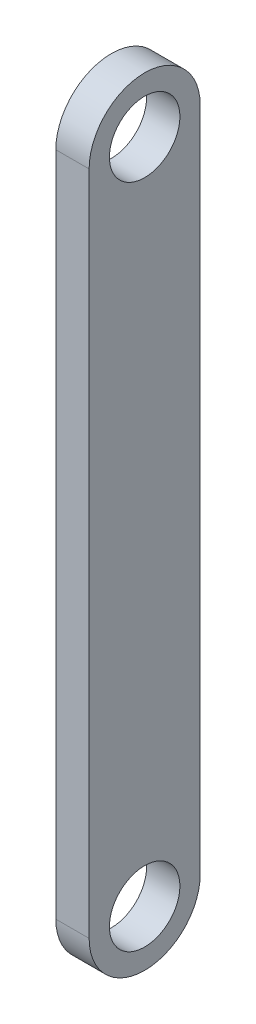
SolidWorks part; units mm, degrees
material "Acrylic (Medium-high impact)"
ref_plane "Alzado" through (0, 0, 0) normal (0, 0, 1) x (1, 0, 0)
ref_plane "Planta" through (0, 0, 0) normal (0, 1, 0) x (1, 0, 0)
ref_plane "Vista lateral" through (0, 0, 0) normal (1, 0, 0) x (0, 0, -1)
sketch "Sketch3" plane through (0, 0, 0) normal (1, 0, 0) x (0, 0, -1)
  line L1 (-5, -35) -> (5, -35)
  line L2 (-5, -35) -> (-5, 35)
  line L3 (-5, 35) -> (5, 35)
  line L4 (5, -35) -> (5, 35)
  line L5 (-5, -35) -> (5, 35) construction
  line L6 (-5, 35) -> (5, -35) construction
  point P0 (0, 0)
  dimension "D1" = 70
  dimension "D2" = 10
extrude "Boss-Extrude1" add sketch "Sketch3" along normal blind 3 contours L3 L4 L1 L2
sketch "Sketch4" plane through (3, 0, 0) normal (1, 0, 0) x (0, 0, -1)
  line L0 (0, 0) -> (0, -35) construction
  line L1 (-5, -35) -> (5, -35) construction
  line L2 (0, 0) -> (0, 35) construction
  line L3 (-5, 35) -> (5, 35) construction
  line L4 (0, 0) -> (0, 30) construction
  line L5 (0, 0) -> (0, -30) construction
  circle A0 centre (0, 30) radius 3.175
  circle A1 centre (0, -30) radius 3.175
  dimension "D1" = 30
  dimension "D2" = 30
extrude "Cut-Extrude1" cut sketch "Sketch4" against normal blind 5
fillet "Fillet2" 2 edges at (1.5, 35, 5) (1.5, 35, -5) type full round first side face at (1.5, 0, 5) second side face at (1.5, 0, -5) middle face at (1.5, 35, 0)
fillet "Fillet3" 2 edges at (1.5, -35, -5) (1.5, -35, 5) type full round first side face at (1.5, -2.5, -5) second side face at (1.5, -2.5, 5) middle face at (1.5, -35, 0)
